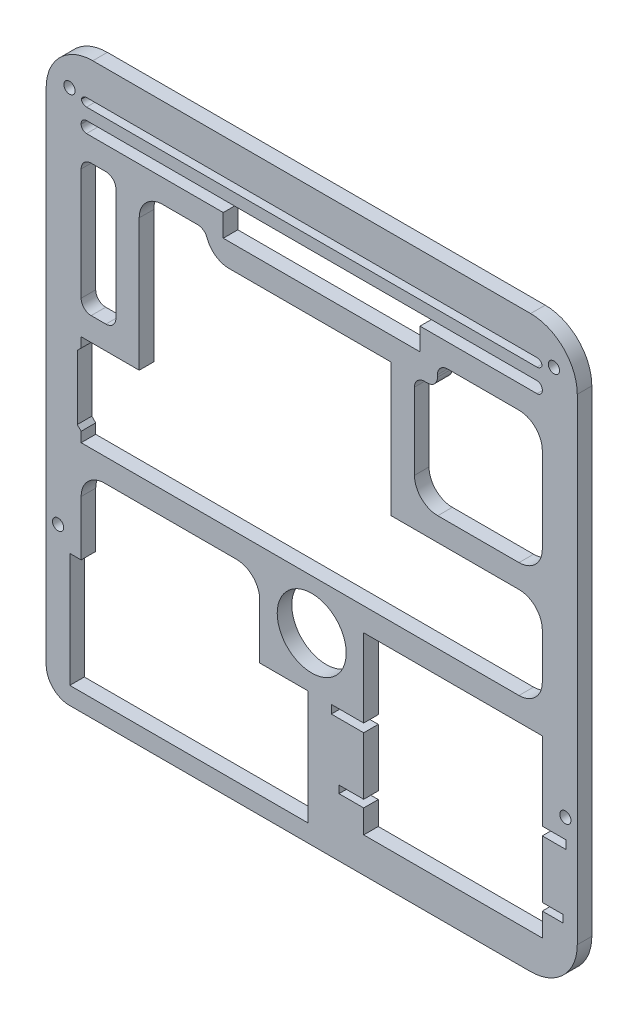
SolidWorks part; units mm, degrees
ref_plane "Front Plane" through (0, 0, 0) normal (0, 0, 1) x (1, 0, 0)
ref_plane "Top Plane" through (0, 0, 0) normal (0, 1, 0) x (1, 0, 0)
ref_plane "Right Plane" through (0, 0, 0) normal (1, 0, 0) x (0, 0, -1)
sketch "Sketch1" plane through (0, 0, 0) normal (0, 0, 1) x (1, 0, 0)
  line L0 (63.9883, 52.5442) -> (63.9883, 48.7342) construction
  line L1 (6.1648, -9.556) -> (64.0322, -9.556)
  line L2 (6.1648, -9.556) -> (6.1648, 52.5442)
  line L3 (6.1648, 52.5442) -> (64.0322, 52.5442)
  line L4 (64.0322, -9.556) -> (64.0322, 52.5442)
  line L5 (60.2222, 48.7342) -> (9.9748, 48.7342)
  line L6 (60.2222, 48.7342) -> (60.2222, -5.746)
  line L7 (60.2222, -5.746) -> (9.9748, -5.746)
  line L8 (9.9748, 48.7342) -> (9.9748, -5.746)
  line L9 (63.9883, 50.6392) -> (18.0707, 50.6392) construction
  line L10 (9.9748, 39.3805) -> (6.1648, 39.3805) construction
  line L11 (8.0698, 39.3805) -> (8.0698, 23.9527) construction
  line L12 (13.5248, -5.746) -> (13.5248, -9.556) construction
  line L13 (13.5248, -7.651) -> (21.1598, -7.651) construction
  line L14 (64.0322, 38.1916) -> (60.2222, 38.1916) construction
  line L15 (62.1272, 38.1916) -> (62.1272, 22.3321) construction
  line L16 (48.6748, 50.6392) -> (23.5288, 50.6392) construction
  line L17 (62.1272, 27.1202) -> (62.1272, 39.363) construction
  line L18 (8.0698, 15.868) -> (8.0698, 3.6252) construction
  line L19 (35.2238, -7.651) -> (34.6952, -7.651) construction
  dimension "D1" = 3.81
  dimension "D2" = 3.81
extrude "Boss-Extrude1" add sketch "Sketch1" along normal blind 1.5875
sketch "Sketch2" plane through (0, 0, 0) normal (0, 0, -1) x (-1, 0, 0)
  line L0 (-60.2222, -5.746) -> (-60.2222, 48.7342) construction
  line L1 (-60.2222, 15.868) -> (-9.9748, 15.868)
  line L2 (-60.2222, 15.868) -> (-60.2222, 13.328)
  line L3 (-60.2222, 13.328) -> (-9.9748, 13.328)
  line L4 (-9.9748, 15.868) -> (-9.9748, 13.328)
  line L5 (-9.9748, 48.7342) -> (-9.9748, -5.746) construction
  line L6 (-13.0532, 15.868) -> (-50.7532, 15.868) construction
  line L8 (-46.8968, 42.9049) -> (-46.8968, 45.3306) construction
  line L9 (-25.4592, 42.9049) -> (-46.8968, 42.9049) construction
  line L10 (-25.4592, 42.9049) -> (-25.4592, 45.3306) construction
  line L11 (-60.2222, 45.3306) -> (-46.8968, 45.3306)
  line L12 (-60.2222, 45.3306) -> (-60.2222, 42.7906)
  line L13 (-60.2222, 42.7906) -> (-48.8018, 42.7906)
  line L14 (-9.9748, 45.3306) -> (-9.9748, 42.7906)
  line L15 (-60.2222, 47.8325) -> (-9.9748, 47.8325)
  line L16 (-60.2222, 47.8325) -> (-60.2222, 46.5625)
  line L17 (-60.2222, 46.5625) -> (-9.9748, 46.5625)
  line L18 (-9.9748, 47.8325) -> (-9.9748, 46.5625)
  line L20 (-55.2788, 45.3306) -> (-16.9248, 45.3306) construction
  line L21 (-55.2788, 46.5625) -> (-16.9248, 46.5625) construction
  line L22 (-46.8968, 42.9049) -> (-46.8968, 45.3306)
  line L23 (-25.4592, 42.9049) -> (-46.8968, 42.9049)
  line L24 (-25.4592, 42.9049) -> (-25.4592, 45.3306)
  line L25 (-48.8018, 42.7906) -> (-48.8018, 40.3649)
  line L26 (-48.8018, 40.3649) -> (-23.5542, 40.3649)
  line L27 (-23.5542, 40.3649) -> (-23.5542, 42.7906)
  line L28 (-23.5542, 42.7906) -> (-9.9748, 42.7906)
  line L29 (-25.4592, 45.3306) -> (-9.9748, 45.3306)
  dimension "D1" = 2.54
  dimension "D2" = 1.905
  dimension "D3" = 2.54
  dimension "D4" = 1.905
  dimension "D5" = 1.27
extrude "Boss-Extrude2" add sketch "Sketch2" against normal up to surface (1.5875 mm away) up to face at (35.0985, 21.4941, 1.5875)
sketch "Sketch3" plane through (0, 0, 0) normal (0, 0, -1) x (-1, 0, 0)
  line L0 (-50.7532, 25.868) -> (-43.7532, 25.868) construction
  line L1 (-50.7532, 25.868) -> (-43.7532, 25.868)
  line L2 (-50.7532, 25.868) -> (-60.2222, 25.868)
  line L3 (-60.2222, 15.868) -> (-60.2222, 42.7906) construction
  line L4 (-60.2222, 25.868) -> (-60.2222, 28.408)
  line L5 (-60.2222, 28.408) -> (-46.2932, 28.408)
  line L6 (-43.7532, 28.408) -> (-43.7532, 25.868)
  line L7 (-43.7532, 28.408) -> (-43.7532, 40.3649)
  line L8 (-48.8018, 40.3649) -> (-23.5542, 40.3649) construction
  line L9 (-43.7532, 40.3649) -> (-46.2932, 40.3649)
  line L10 (-46.2932, 40.3649) -> (-46.2932, 28.408)
  line L11 (-16.3032, 25.868) -> (-13.0532, 25.868) construction
  line L12 (-16.3032, 25.868) -> (-13.0532, 25.868)
  line L13 (-13.0532, 25.868) -> (-9.9748, 25.868)
  line L14 (-9.9748, 42.7906) -> (-9.9748, 15.868) construction
  line L15 (-9.9748, 25.868) -> (-9.9748, 28.408)
  line L16 (-9.9748, 28.408) -> (-13.7632, 28.408)
  line L17 (-13.7632, 28.408) -> (-13.7632, 42.7906)
  line L18 (-23.5542, 42.7906) -> (-9.9748, 42.7906) construction
  line L19 (-13.7632, 42.7906) -> (-16.3032, 42.7906)
  line L20 (-16.3032, 42.7906) -> (-16.3032, 25.868)
  line L21 (-16.3032, 25.868) -> (-16.2412, 25.8471)
  line M22 (-60.2222, 15.868) -> (-60.2222, 42.7906)
  line M25 (-48.8018, 40.3649) -> (-23.5542, 40.3649)
  line M27 (-23.5542, 42.7906) -> (-9.9748, 42.7906)
  line M28 (-9.9748, 42.7906) -> (-9.9748, 15.868)
  dimension "D1" = 2.54
  dimension "D2" = 2.54
  dimension "D3" = 2.54
  dimension "D4" = 2.54
extrude "Boss-Extrude3" add sketch "Sketch3" against normal up to surface (1.5875 mm away) contours L10 L5 L2 L1 L6 L7 M25 M22 | L20 L12 L13 L16 L17 M27 M28 region at (55.4877, 26.0875, 0) region at (14.4544, 33.0139, 0) up to face at (35.0985, 48.2834, 1.5875)
sketch "Sketch4" plane through (0, 0, 0) normal (0, 0, -1) x (-1, 0, 0)
  line L0 (-60.2222, 13.328) -> (-9.9748, 13.328) construction
  line L1 (-40.7627, 13.328) -> (-29.4343, 13.328)
  line L2 (-40.7627, 13.328) -> (-40.7627, -5.746)
  line L3 (-40.7627, -5.746) -> (-29.4343, -5.746)
  line L4 (-29.4343, 13.328) -> (-29.4343, -5.746)
  line L5 (-9.9748, -5.746) -> (-60.2222, -5.746) construction
  line L6 (-38.8577, 10.4578) -> (-40.7627, 10.4578) construction
  line L7 (-31.3393, 10.4578) -> (-29.4343, 10.4578) construction
  circle A0 centre (-35.0985, 10.4578) radius 3.7592 construction
  dimension "D1" = 1.905
extrude "Boss-Extrude4" add sketch "Sketch4" against normal up to surface (1.5875 mm away) up to face at (11.869, 35.5993, 1.5875)
sketch "Sketch5" plane through (0, 0, 0) normal (0, 0, -1) x (-1, 0, 0)
  line L0 (-8.7364, 4.8077) -> (-34.6952, 4.8077) construction
  line L3 (-34.6952, -7.651) -> (-34.6952, 4.8077) construction
  line L4 (-8.7364, -7.651) -> (-34.6952, -7.651) construction
  line L5 (-8.7364, -7.651) -> (-8.7364, 4.8077) construction
  line L6 (-8.7364, 4.8077) -> (-34.6952, 4.8077)
  line L7 (-34.6952, -7.651) -> (-34.6952, 4.8077)
  line L8 (-8.7364, -7.651) -> (-34.6952, -7.651)
  line L9 (-8.7364, -7.651) -> (-8.7364, 4.8077)
  circle A0 centre (-35.0985, 10.4578) radius 3.7592 construction
  circle A1 centre (-35.0985, 10.4578) radius 3.7592
extrude "Cut-Extrude1" cut sketch "Sketch5" against normal up to surface (1.5875 mm away) up to face at (50.4924, 3.791, 1.5875)
fillet "Fillet1" radius 5.08 3 edges at (64.0322, -9.556, 0.7937) (6.1648, 52.5442, 0.7937) (64.0322, 52.5442, 0.7937)
fillet "Fillet2" radius 2.54 9 edges at (16.3032, 42.7906, 0.7937) (23.5542, 40.3649, 0.7937) (60.2222, 42.7906, 0.7937) (46.2932, 28.408, 0.7937) (60.2222, 15.868, 0.7937) (60.2222, 28.408, 0.7937) (9.9748, 13.328, 0.7937) (29.4343, 13.328, 0.7937) (60.2222, 25.868, 0.7937)
fillet "Fillet3" radius 1.0922 8 edges at (46.2932, 40.3649, 0.7937) (48.8018, 40.3649, 0.7937) (48.8018, 42.7906, 0.7937) (9.9748, 28.408, 0.7937) (13.7632, 28.408, 0.7937) (9.9748, 42.7906, 0.7937) (13.7632, 42.7906, 0.7937) (23.5542, 42.7906, 0.7937)
fillet "Fillet4" radius 0.5842 8 edges at (9.9748, 45.3306, 0.7937) (9.9748, 47.8325, 0.7937) (9.9748, 48.7342, 0.7937) (9.9748, 46.5625, 0.7937) (60.2222, 47.8325, 0.7937) (60.2222, 48.7342, 0.7937) (60.2222, 46.5625, 0.7937) (60.2222, 45.3306, 0.7937)
fillet "Fillet5" radius 2.54 1 edges at (6.1648, -9.556, 0.7937)
sketch "Sketch6" plane through (0, 0, 0) normal (0, 0, -1) x (-1, 0, 0)
  line L0 (-9.5532, 17.368) -> (-11.0532, 15.868) construction
  line L1 (-11.0532, 25.868) -> (-9.5532, 24.368) construction
  line L2 (-9.5532, 24.368) -> (-9.5532, 17.368) construction
  line L3 (-9.5532, 17.368) -> (-11.0532, 15.868)
  line L4 (-11.0532, 25.868) -> (-9.5532, 24.368)
  line L5 (-9.5532, 24.368) -> (-9.5532, 17.368)
  line L6 (-11.0532, 25.868) -> (-11.0532, 15.868)
  circle A4 centre (-61.4922, 48.7342) radius 0.6096 construction
  circle A5 centre (-61.4922, 48.7342) radius 0.6096
  circle A6 centre (-7.4602, 6.9018) radius 0.6096 construction
  circle A7 centre (-7.4602, 6.9018) radius 0.6096
  circle A8 centre (-62.7368, 6.9018) radius 0.6096 construction
  circle A9 centre (-62.7368, 6.9018) radius 0.6096
  circle A10 centre (-8.7048, 48.7342) radius 0.6096 construction
  circle A11 centre (-8.7048, 48.7342) radius 0.6096
extrude "Cut-Extrude2" cut sketch "Sketch6" against normal up to surface (1.5875 mm away) up to face at (31.3393, 10.4578, 1.5875)
sketch "Sketch7" plane through (0, 0, 0) normal (0, 0, -1) x (-1, 0, 0)
  line L0 (-37.2352, 4.8077) -> (-62.813, 4.8077) construction
  line L1 (-62.813, 4.8077) -> (-62.813, 3.8933) construction
  line L2 (-62.813, 3.8933) -> (-37.2352, 3.8933) construction
  line L3 (-37.2352, 3.8933) -> (-37.2352, 4.8077) construction
  line L4 (-38.0692, -2.3887) -> (-62.4532, -2.3887) construction
  line L5 (-62.4532, -2.3887) -> (-62.4532, -3.2015) construction
  line L6 (-62.4532, -3.2015) -> (-38.0692, -3.2015) construction
  line L7 (-38.0692, -3.2015) -> (-38.0692, -2.3887) construction
  line L8 (-37.2352, 4.8077) -> (-62.813, 4.8077)
  line L9 (-62.813, 4.8077) -> (-62.813, 3.8933)
  line L10 (-62.813, 3.8933) -> (-37.2352, 3.8933)
  line L11 (-37.2352, 3.8933) -> (-37.2352, 4.8077)
  line L12 (-38.0692, -2.3887) -> (-62.4532, -2.3887)
  line L13 (-62.4532, -2.3887) -> (-62.4532, -3.2015)
  line L14 (-62.4532, -3.2015) -> (-38.0692, -3.2015)
  line L15 (-38.0692, -3.2015) -> (-38.0692, -2.3887)
extrude "Cut-Extrude3" cut sketch "Sketch7" against normal up to surface (1.5875 mm away) up to face at (8.0952, 48.7342, 1.5875)
